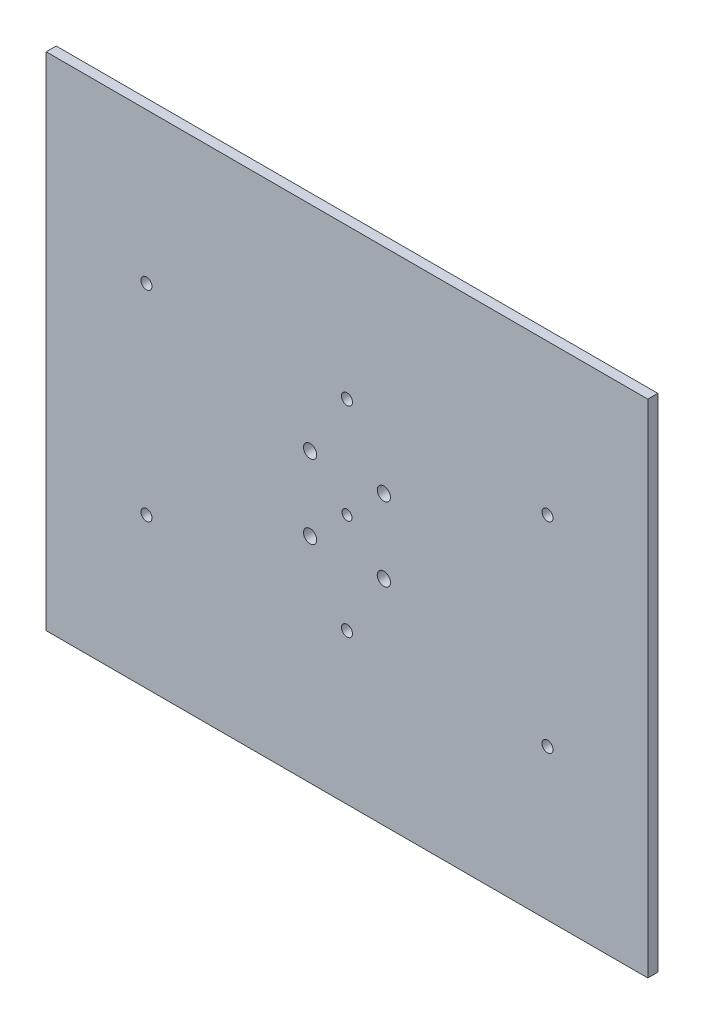
SolidWorks part; units mm, degrees
ref_plane "前视基准面" through (0, 0, 0) normal (0, 0, 1) x (1, 0, 0)
ref_plane "上视基准面" through (0, 0, 0) normal (0, 1, 0) x (1, 0, 0)
ref_plane "右视基准面" through (0, 0, 0) normal (1, 0, 0) x (0, 0, -1)
sketch "草图1" plane through (0, 0, 0) normal (0, 0, 1) x (1, 0, 0)
  line L0 (-18.3848, 18.3848) -> (0, 0) construction
  line L1 (150, -125) -> (-150, -125)
  line L2 (150, -125) -> (150, 125)
  line L3 (150, 125) -> (-150, 125)
  line L4 (-150, -125) -> (-150, 125)
  line L5 (150, -125) -> (-150, 125) construction
  line L6 (150, 125) -> (-150, -125) construction
  line L7 (0, 0) -> (0, 75.2853) construction
  line L8 (0, 0) -> (89.5261, 0) construction
  circle A0 centre (-18.3848, 18.3848) radius 3.3
  circle A1 centre (18.3848, 18.3848) radius 3.3
  circle A2 centre (18.3848, -18.3848) radius 3.3
  circle A3 centre (-18.3848, -18.3848) radius 3.3
  circle A4 centre (0, 0) radius 2.5
  point P0 (0, 0)
  dimension "D3" = 6.6
  dimension "D6" = 5
  dimension "D1" = 250
  dimension "D2" = 300
  dimension "D4" = 26
  dimension "D5" = 45
extrude "凸台-拉伸1" add sketch "草图1" along normal blind 5
sketch "草图2" plane through (0, 0, 5) normal (0, 0, 1) x (1, 0, 0)
  line L0 (-150, 0) -> (150, 0) construction
  line L1 (-150, 125) -> (-150, -125) construction
  line L2 (150, -125) -> (150, 125) construction
  line L3 (0, 125) -> (0, -125) construction
  line L4 (150, 125) -> (-150, 125) construction
  line L5 (-150, -125) -> (150, -125) construction
  line L7 (100, -50) -> (-100, -50) construction
  line L8 (100, -50) -> (100, 50) construction
  line L9 (100, 50) -> (-100, 50) construction
  line L10 (-100, -50) -> (-100, 50) construction
  line L11 (100, -50) -> (-100, 50) construction
  line L12 (100, 50) -> (-100, -50) construction
  circle A0 centre (-100, 50) radius 2.75
  circle A1 centre (0, 50) radius 2.75
  circle A2 centre (100, 50) radius 2.75
  circle A3 centre (100, -50) radius 2.75
  circle A4 centre (0, -50) radius 2.75
  circle A5 centre (-100, -50) radius 2.75
  point P12 (0, 0)
  dimension "D1" = 5.5
  dimension "D2" = 100
  dimension "D3" = 200
extrude "切除-拉伸1" cut sketch "草图2" against normal through all
